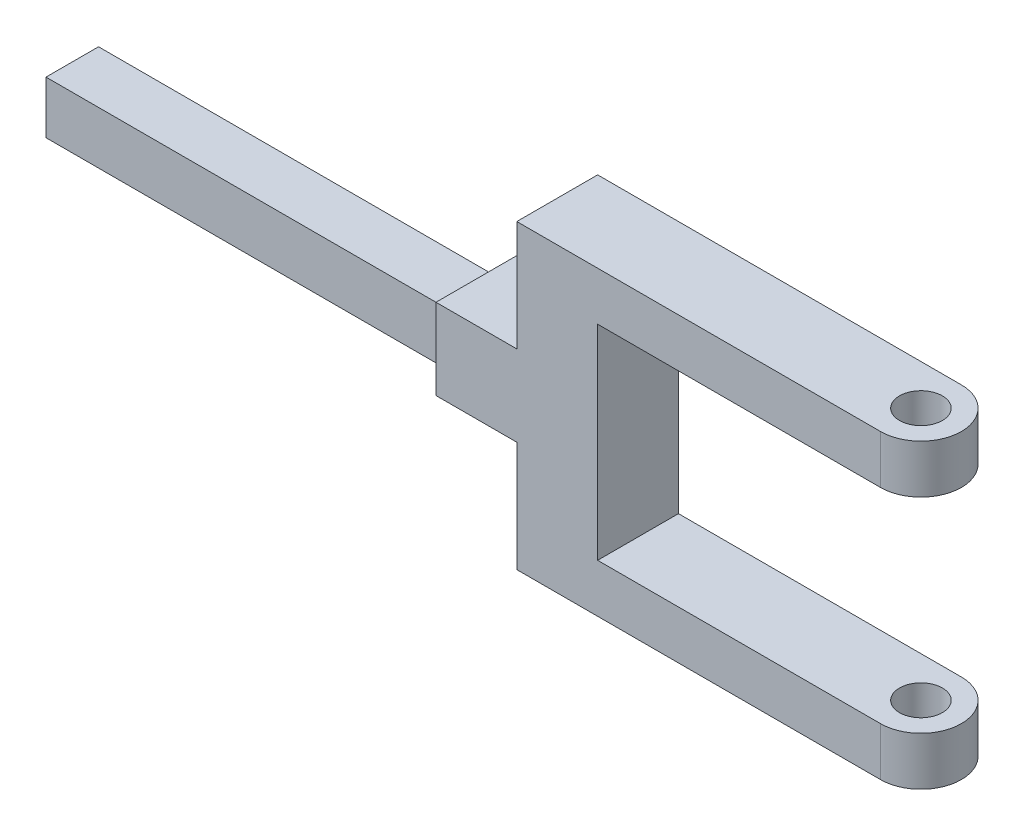
SolidWorks part; units mm, degrees
ref_plane "前视基准面" through (0, 0, 0) normal (0, 0, 1) x (1, 0, 0)
ref_plane "上视基准面" through (0, 0, 0) normal (0, 1, 0) x (1, 0, 0)
ref_plane "右视基准面" through (0, 0, 0) normal (1, 0, 0) x (0, 0, -1)
other "Configuration Table"
sketch "草图1" plane through (0, 0, 0) normal (0, 0, 1) x (1, 0, 0)
  line L0 (0, 12.65) -> (0, -12.65)
  line L1 (0, 12.65) -> (40, 12.65)
  line L2 (40, 12.65) -> (40, 18.65)
  line L3 (40, 18.65) -> (-10, 18.65)
  line L4 (-10, 18.65) -> (-10, -18.65)
  line L5 (-10, -18.65) -> (40, -18.65)
  line L6 (40, -18.65) -> (40, -12.65)
  line L7 (40, -12.65) -> (0, -12.65)
  point P4 (0, 0)
  dimension "D1" = 25.3
  dimension "D2" = 40
  dimension "D3" = 6
  dimension "D4" = 10
extrude "凸台-拉伸1" add sketch "草图1" along normal blind 10
sketch "草图2" plane through (-10, 0, 0) normal (-1, 0, 0) x (0, 0, 1)
  line L0 (8.25, 3.25) -> (8.25, -3.25)
  line L1 (1.75, -3.25) -> (8.25, -3.25)
  line L2 (1.75, 3.25) -> (1.75, -3.25)
  line L3 (1.75, 3.25) -> (8.25, 3.25)
  line L4 (5, 18.65) -> (5, -18.65) construction
  line L5 (0, 0) -> (10, 0) construction
  line L7 (0, 5) -> (10, 5)
  line L8 (0, 18.65) -> (0, -18.65)
  line L9 (0, -18.65) -> (10, -18.65)
  line L10 (10, -18.65) -> (10, 18.65)
  line L11 (10, 18.65) -> (0, 18.65)
  line L12 (0, 18.65) -> (0, -18.65)
  line L13 (0, -18.65) -> (10, -18.65)
  line L14 (10, -18.65) -> (10, 18.65)
  line L15 (10, 18.65) -> (0, 18.65)
  line L16 (0, 5) -> (0, -5)
  line L17 (0, -5) -> (10, -5)
  line L18 (10, 5) -> (10, -5)
  line L19 (5, -5) -> (5, 5) construction
  line L20 (0, 0) -> (10, 0) construction
  line L21 (1.5, 3.5) -> (8.5, 3.5) construction
  line L22 (1.5, 3.5) -> (1.5, -3.5) construction
  line L23 (1.5, -3.5) -> (8.5, -3.5) construction
  line L24 (8.5, 3.5) -> (8.5, -3.5) construction
  line L25 (5, -3.5) -> (5, 3.5) construction
  line L26 (1.5, 0) -> (8.5, 0) construction
  point P6 (5, 0)
  point P13 (5, 0)
  line M8 (0, 18.65) -> (0, -18.65)
  dimension "D2" = 10
  dimension "D3" = 1.5
  dimension "D4" = 0.25
  dimension "D1" = 0
extrude "凸台-拉伸2" add sketch "草图2" along normal blind 10 contours L17 L14 L7 L2 L3 L0 L1 M8 | L3 L2 L1 L0 region at (-10, 0, 5) region at (-10, 4.8586, 5)
extrude "凸台-拉伸3" add sketch "草图2<3>" along normal blind 50 from surface contours L3 L2 L1 L0 region at (-10, 0, 5) starting at face at (-20, 0, 5)
sketch "草图2<3>" plane through (-10, 0, 0) normal (-1, 0, 0) x (0, 0, 1) same geometry as "草图2"
sketch "草图3" plane through (0, 18.65, 0) normal (0, 1, 0) x (1, 0, 0)
  line L0 (-10, -5) -> (40, -5) construction
  line L1 (-10, 0) -> (-10, -10) construction
  line L2 (40, -10) -> (40, 0) construction
  line L3 (40, 0) -> (-10, 0) construction
  circle A0 centre (35, -5) radius 5
  circle A1 centre (35, -5) radius 2.65
  line M1 (40, 0) -> (-10, 0)
  line M3 (-10, -10) -> (40, -10)
  line M4 (40, -10) -> (40, 0)
  dimension "D1" = 5.3
extrude "切除-拉伸1" cut sketch "草图3" against normal through all contours A1 L0 | L0 A1 | A0 M4 M1 | A0 M3 M4 region at (35, 18.65, 6.1247) region at (35, 18.65, 3.8753) region at (38.8832, 18.65, 8.8832) region at (38.8832, 18.65, 1.1168)
